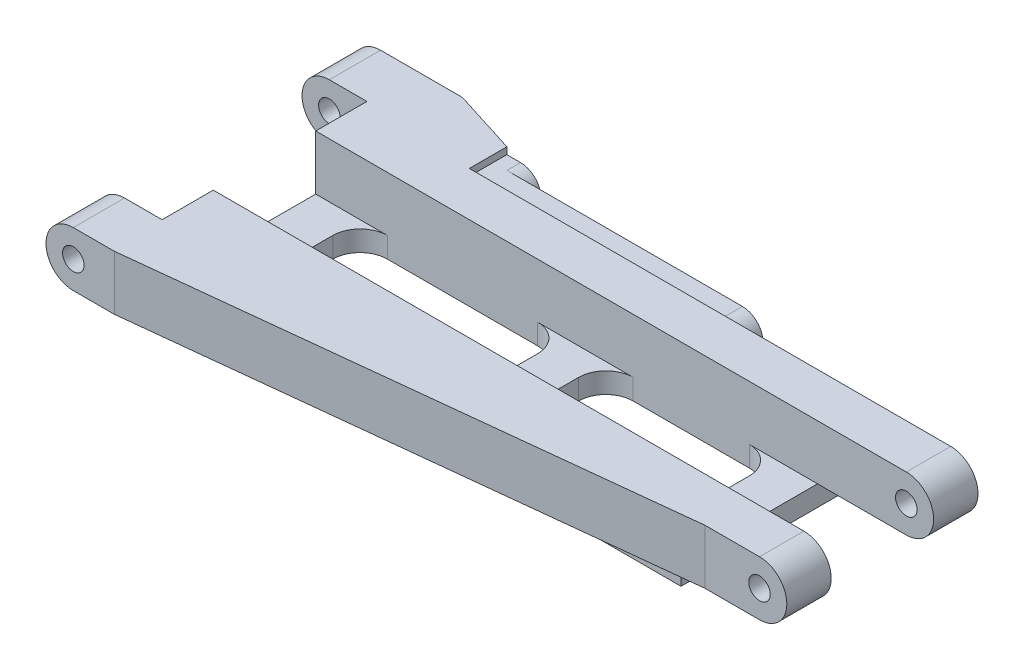
SolidWorks part; units mm, degrees
ref_plane "Front Plane" through (0, 0, 0) normal (0, 0, 1) x (1, 0, 0)
ref_plane "Top Plane" through (0, 0, 0) normal (0, 1, 0) x (1, 0, 0)
ref_plane "Right Plane" through (0, 0, 0) normal (1, 0, 0) x (0, 0, -1)
other "Front"
sketch "Sketch1" plane through (0, 0, 0) normal (0, 1, 0) x (1, 0, 0)
  line L0 (-35, 6.5) -> (0, 6.5)
  line L1 (0, 6.5) -> (0, 0)
  line L2 (0, 0) -> (-90.5, 0)
  line L3 (-90.5, 7.5) -> (-90.5, 0)
  line L4 (-90.5, -15) -> (0, -15)
  line L5 (0, -15) -> (0, -21.5)
  line L6 (0, -21.5) -> (-12, -21.5)
  line L7 (-12, -21.5) -> (-90, -30)
  line L8 (-90, -30) -> (-100, -30)
  line L9 (-100, -30) -> (-100, -22.5)
  line L10 (-100, -22.5) -> (-90.5, -22.5)
  line L11 (-90.5, -15) -> (-90.5, -22.5)
  line L12 (-90.5, 7.5) -> (-100, 7.5)
  line L13 (-100, 7.5) -> (-100, 15)
  line L14 (-100, 15) -> (-84, 15)
  line L15 (-84, 15) -> (-74.5, 12)
  line L16 (-74.5, 12) -> (-69.5, 12)
  line L17 (-69.5, 12) -> (-69.5, 10)
  line L18 (-69.5, 10) -> (-35, 10)
  line L19 (-35, 10) -> (-35, 6.5)
  dimension "D1" = 28
  dimension "D2" = 6.5
  dimension "D3" = 6.5
  dimension "D4" = 45
  dimension "D5" = 7.5
  dimension "D6" = 7.5
  dimension "D7" = 8.5
  dimension "D8" = 10
  dimension "D9" = 12
  dimension "D10" = 35
  dimension "D11" = 100
  dimension "D12" = 9.5
  dimension "D13" = 34.5
  dimension "D14" = 16
  dimension "D15" = 10
  dimension "D16" = 12
  dimension "D17" = 5
extrude "Rails" add sketch "Sketch1" along normal blind 8 contours L2 L3 L12 L13 L14 L15 L16 L17 L18 L19 L0 L1 | L4 L5 L6 L7 L8 L9 L10 L11
fillet "Fillet3" 2 edges at (0, 8, 18.25) (0, 0, 18.25) type full round first side face at (-60.375, 8, 22.25) second side face at (-60.375, 0, 22.25) middle face at (0, 4, 18.25)
fillet "Fillet4" 2 edges at (0, 8, -3.25) (0, 0, -3.25) type full round first side face at (-62.375, 8, -8.5) second side face at (-62.375, 0, -8.5) middle face at (0, 4, -3.25)
fillet "Fillet5" 2 edges at (-100, 8, -11.25) (-100, 0, -11.25) type full round first side face at (-63.0417, 8, -8.5) second side face at (-63.0417, 0, -8.5) middle face at (-100, 4, -11.25)
fillet "Fillet6" 2 edges at (-100, 8, 26.25) (-100, 0, 26.25) type full round first side face at (-61.375, 8, 22.25) second side face at (-61.375, 0, 22.25) middle face at (-100, 4, 26.25)
sketch "Sketch2" plane through (0, 0, -10) normal (0, 0, -1) x (-1, 0, 0)
  line L0 (69.5, 8) -> (69.5, 0) construction
  line L1 (35, 0) -> (69.5, 0)
  line L2 (35, 0) -> (35, 1)
  line L3 (35, 1) -> (69.5, 1)
  line L4 (69.5, 0) -> (69.5, 1)
  line L6 (35, 8) -> (69.5, 8)
  line L7 (35, 8) -> (35, 7)
  line L8 (35, 7) -> (69.5, 7)
  line L9 (69.5, 8) -> (69.5, 7)
  dimension "D1" = 1
  dimension "D2" = 1
extrude "Cut-Extrude1" cut sketch "Sketch2" against normal blind 3.5
sketch "Sketch3" plane through (0, 0, -12) normal (0, 0, -1) x (-1, 0, 0)
  line L0 (69.5, 8) -> (69.5, 0) construction
  line L1 (74.5, 8) -> (69.5, 8)
  line L2 (74.5, 8) -> (74.5, 7)
  line L3 (74.5, 7) -> (69.5, 7)
  line L4 (69.5, 8) -> (69.5, 7)
  line L5 (69.5, 7) -> (69.5, 1) construction
  line L7 (74.5, 0) -> (69.5, 0)
  line L8 (74.5, 0) -> (74.5, 1)
  line L9 (74.5, 1) -> (69.5, 1)
  line L10 (69.5, 0) -> (69.5, 1)
  dimension "D1" = 1
extrude "Cut-Extrude2" cut sketch "Sketch3" against normal up to surface (5.5 mm away) up to face at (-44, 4, -6.5)
fillet "Fillet9" 2 edges at (-35, 7, -8.25) (-35, 1, -8.25) type full round first side face at (-59.6667, 7, -9.5) second side face at (-59.6667, 1, -9.5) middle face at (-35, 4, -8.25)
fillet "Fillet10" 2 edges at (-69.5, 7, -11) (-69.5, 1, -11) type full round first side face at (-60.6667, 7, -9.5) second side face at (-60.6667, 1, -9.5) middle face at (-69.5, 4, -11)
sketch "Sketch4" plane through (0, 0, 0) normal (0, -1, 0) x (1, 0, 0)
  line L0 (-17, 20) -> (-17, -5)
  line L1 (-17, -5) -> (-90.5, -5)
  line L2 (-90.5, -5) -> (-90.5, 20)
  line L3 (-90.5, 20) -> (-17, 20)
  line L4 (-90.5, -7.5) -> (-90.5, 0) construction
  line L5 (0, -6.5) -> (0, 0) construction
  line L6 (-90.5, 15) -> (-4, 15) construction
  line L7 (-4, 0) -> (-90.5, 0) construction
  line L8 (-27, 0) -> (-44, 0)
  line L9 (-23, 4) -> (-23, 11)
  line L10 (-27, 15) -> (-44, 15)
  line L11 (-48, 4) -> (-48, 11)
  line L13 (-58, 0) -> (-80, 0)
  line L14 (-54, 4) -> (-54, 11)
  line L15 (-58, 15) -> (-80, 15)
  line L16 (-84, 4) -> (-84, 11)
  arc A0 (-54, 11) -> (-58, 15) centre (-58, 11) ccw
  arc A1 (-80, 15) -> (-84, 11) centre (-80, 11) ccw
  arc A2 (-80, 0) -> (-84, 4) centre (-80, 4) cw
  arc A3 (-58, 0) -> (-54, 4) centre (-58, 4) ccw
  arc A4 (-44, 0) -> (-48, 4) centre (-44, 4) cw
  arc A5 (-44, 15) -> (-48, 11) centre (-44, 11) ccw
  arc A6 (-23, 11) -> (-27, 15) centre (-27, 11) ccw
  arc A7 (-27, 0) -> (-23, 4) centre (-27, 4) ccw
  point P22 (-54, 15)
  point P25 (-84, 15)
  point P30 (-54, 0)
  point P35 (-48, 15)
  point P38 (-23, 15)
  point P41 (-23, 0)
  dimension "D8" = 4
  dimension "D1" = 25
  dimension "D2" = 17
  dimension "D3" = 5
  dimension "D4" = 6
  dimension "D5" = 6
  dimension "D6" = 25
  dimension "D7" = 30
extrude "Boss-Extrude2" add sketch "Sketch4" along normal blind 3
sketch "Sketch5" plane through (0, 0, 30) normal (0, 0, 1) x (1, 0, 0)
  circle A0 centre (-96, 4) radius 1.575
  arc A1 (-96, 8) -> (-96, 0) centre (-96, 4) ccw construction
  circle A2 centre (-4, 4) radius 1.575
  arc A3 (-4, 0) -> (-4, 8) centre (-4, 4) ccw construction
  dimension "D1" = 3.15
  dimension "D2" = 3.15
extrude "Cut-Extrude3" cut sketch "Sketch5" against normal through all both and the other way through all
sketch "Sketch6" plane through (0, 0, -10) normal (0, 0, -1) x (-1, 0, 0)
  circle A0 centre (43, 4) radius 1.5
  arc A1 (38, 7) -> (38, 1) centre (38, 4) ccw construction
  arc A2 (4, 8) -> (4, 0) centre (4, 4) ccw construction
  point P6 (35, 4)
  point P11 (0, 4)
  dimension "D1" = 3
  dimension "D2" = 43
extrude "Cut-Extrude4" cut sketch "Sketch6" against normal blind 3 contours A0
sketch "Sketch7" plane through (0, 0, -10) normal (0, 0, -1) x (-1, 0, 0)
  line L0 (74.5, 1) -> (38, 1) construction
  circle A0 centre (53, 4) radius 1.5
  circle A2 centre (96, 4) radius 1.575 construction
  point P2 (0, 0)
  dimension "D1" = 3
  dimension "D2" = 3
  dimension "D3" = 43
extrude "Cut-Extrude5" [suppressed] cut sketch "Sketch7" against normal up to surface (3.5 mm away) up to face at (-5.575, 4, -6.5)
